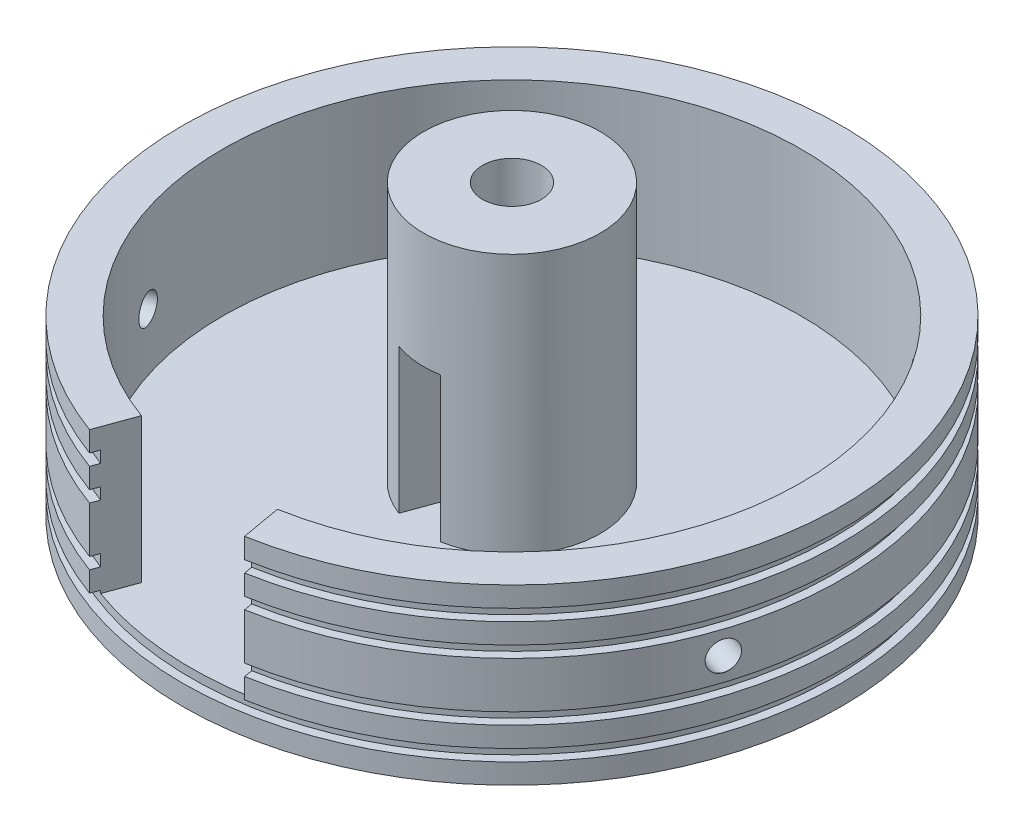
SolidWorks part; units mm, degrees
material "6061-T6 (SS)"
ref_plane "Front Plane" through (0, 0, 0) normal (0, 0, 1) x (1, 0, 0)
ref_plane "Top Plane" through (0, 0, 0) normal (0, 1, 0) x (1, 0, 0)
ref_plane "Right Plane" through (0, 0, 0) normal (1, 0, 0) x (0, 0, -1)
sketch "Sketch1" plane through (0, 0, 0) normal (0, 0, 1) x (1, 0, 0)
  line L0 (0, 0) -> (0, 50000) construction
  line L11 (0, 0) -> (0, 50)
  line L12 (0, 50) -> (15.25, 50)
  line L13 (15.25, 50) -> (15.25, 5)
  line L14 (15.25, 5) -> (50, 5)
  line L15 (50, 5) -> (50, 30)
  line L16 (50, 30) -> (57, 30)
  line L17 (57, 30) -> (57, 26.5)
  line L18 (62.7, 0) -> (-62.7, 0) construction
  line L19 (57, 0) -> (0, 0)
  line L21 (57, 26.5) -> (55.5, 26.5)
  line L23 (57, 24.5) -> (55.5, 24.5)
  line L24 (55.5, 26.5) -> (55.5, 24.5)
  line L25 (57, 21) -> (55.5, 21)
  line L27 (57, 19) -> (55.5, 19)
  line L28 (55.5, 21) -> (55.5, 19)
  line L29 (57, 11) -> (55.5, 11)
  line L31 (57, 9) -> (55.5, 9)
  line L32 (55.5, 11) -> (55.5, 9)
  line L33 (57, 5.5) -> (55.5, 5.5)
  line L35 (57, 3.5) -> (55.5, 3.5)
  line L36 (55.5, 5.5) -> (55.5, 3.5)
  line L37 (57, 24.5) -> (57, 21)
  line L39 (57, 19) -> (57, 11)
  line L41 (57, 9) -> (57, 5.5)
  line L42 (57, 3.5) -> (57, 0)
  dimension "D1" = 30.5
  dimension "D2" = 50
  dimension "D3" = 30
  dimension "D4" = 5
  dimension "D5" = 114
  dimension "D6" = 100
  dimension "D7" = 8
  dimension "D8" = 2
  dimension "D9" = 1.5
revolve "Revolve1" add sketch "Sketch1" angle 360 about L0
hole_wizard "M5 Tapped Hole1" positions "3DSketch1" profile "Sketch2" tap size "M5" standard "ISO" end condition up to next
sketch3d "3DSketch1"
  point P16 (0, 15, 57)
  dimension "D1" = 15
sketch "Sketch2" plane through (0, 15, 57) normal (1, 0, 0) x (0, -1, 0)
  line L0 (0, 0) -> (0, 7)
  line L1 (0, 7) -> (2.5, 7)
  line L2 (2.5, 7) -> (2.5, 0.025)
  line L3 (2.5, 0.025) -> (2.525, 0)
  line L5 (2.525, 0) -> (0, 0)
  line L6 (-2.5, 0.025) -> (-2.525, 0) construction
  line L11 (0, -6.35) -> (0, 107.95) construction
  dimension "Thread Major Dia." = 5
  dimension "Thru Tap Drill Depth" = 7
  dimension "Near C'Sink Dia." = 5.05
  dimension "Near C'Sink Angle" = 90
pattern_circular "CirPattern1" count 5 over 360 about axis through (0, 0, 0) along (0, -1, 0) of "M5 Tapped Hole1" reverse direction yes
hole_wizard "M12 Tapped Hole1" positions "Sketch3" profile "Sketch4" tap size "M12" standard "ISO" end condition up to next
sketch "Sketch3" plane through (0, 0, 0) normal (0, 1, 0) x (1, 0, 0)
  point P15 (0, 0)
sketch "Sketch4" plane through (0, 0, 0) normal (1, 0, 0) x (0, 0, -1)
  line L0 (0, 0) -> (0, 50)
  line L1 (0, 50) -> (5.1, 50)
  line L2 (5.1, 50) -> (5.1, 0)
  line L5 (5.1, 0) -> (0, 0)
  line L11 (0, -6.35) -> (0, 107.95) construction
  dimension "Thru Tap Drill Dia." = 10.2
  dimension "Thru Tap Drill Depth" = 50
cosmetic thread "Hole Thread10" parameters "D2"=12
sketch "Sketch6" plane through (0, 0, 0) normal (0, 1, 0) x (1, 0, 0)
  line L0 (0, 0) -> (9.8979, -56.134)
  line L1 (-19.4951, -53.5625) -> (0, 0)
  line L2 (-27.5, 0) -> (27.5, 0) construction
  arc A0 (-19.4951, -53.5625) -> (9.8979, -56.134) centre (0, 0) ccw
  circle A1 centre (0, 0) radius 57 construction
  dimension "D1" = 30
  dimension "D2" = 110
extrude "Cut-Extrude1" cut sketch "Sketch6" along normal up to surface (30 mm away) from surface up to face at (0, 30, -50) starting at face at (0, 5, -15.25)
equation "\"CanSat_Len\"= 400mm"
equation "\"CanSat_Dia\"= 150mm"
equation "\"BodyTube_ID\"= 114mm"
equation "\"BodyTube_OD\"= 120mm"
equation "\"PayLoadBay_ID\"= 164mm"
equation "\"PayLoadBay_OD\"= 170mm"
equation "\"ParachuteBay_Pitch\"= 400mm"
equation "\"ElectronicsTray_PitchDist\"= 50mm"
equation "\"ElectronicsTray_Height\"= 140mm"
equation "\"D5@Sketch1\"=\"BodyTube_ID\""
